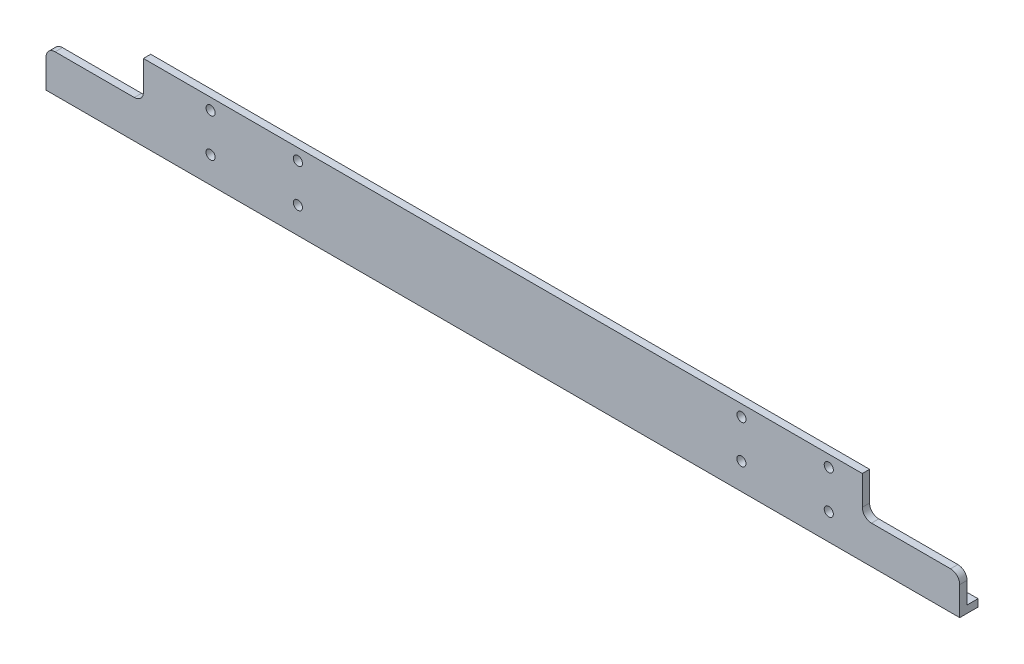
SolidWorks part; units mm, degrees
ref_plane "Front" through (0, 0, 0) normal (0, 0, 1) x (1, 0, 0)
ref_plane "Top" through (0, 0, 0) normal (0, 1, 0) x (1, 0, 0)
ref_plane "Right" through (0, 0, 0) normal (1, 0, 0) x (0, 0, -1)
ref_axis "side-side" through (80.9, 0, 0) along (-1, 0, 0)
ref_axis "up-down" through (0, 50, 0) along (0, -1, 0)
ref_axis "front-back" through (0, 0, -80.9) along (0, 0, 1)
sketch "Sketch1" plane through (0, 0, 0) normal (1, 0, 0) x (0, 0, -1)
  line L1 (0, 0) -> (31.75, 0)
  line L2 (0, 0) -> (0, 31.75)
  line L3 (0, 31.75) -> (3.048, 31.75)
  line L4 (31.75, 0) -> (31.75, 3.048)
  line L5 (3.048, 3.048) -> (31.75, 3.048)
  line L6 (3.048, 3.048) -> (3.048, 31.75)
  dimension "D1" = 31.75
  dimension "D2" = 3.048
extrude "Boss-Extrude1" add sketch "Sketch1" along normal mid plane 381
sketch "Sketch2" plane through (0, 0, 0) normal (0, 0, 1) x (1, 0, 0)
  line L2 (152.877, 19.5) -> (185.5, 19.5)
  line L3 (149.877, 32) -> (149.877, 22.5)
  line L6 (174.5, 4) -> (174.5, 0)
  line L7 (172.5, 4) -> (174.5, 4)
hole_wizard "#6 Clearance Hole1" positions "Sketch4" profile "Sketch3" hole size "#6" standard "ANSI Inch" end condition through all
sketch "Sketch4" plane through (0, 0, 0) normal (0, 0, 1) x (1, 0, 0)
  point P0 (135.9, 27)
  point P3 (135.9, 11)
  point P6 (99.5, 27)
  point P9 (99.468, 11)
  point P12 (-121.868, 27)
  point P15 (-121.868, 11)
  point P18 (-85.468, 11)
  point P21 (-85.468, 27)
sketch "Sketch3" plane through (135.9, 27, 0) normal (1, 0, 0) x (0, -1, 0)
  line L0 (0, 0) -> (0, 31.75)
  line L1 (0, 31.75) -> (1.8986, 31.75)
  line L2 (1.8986, 31.75) -> (1.8986, 0)
  line L5 (1.8986, 0) -> (0, 0)
  line L11 (0, -6.35) -> (0, 107.95) construction
  dimension "Thru Hole Dia." = 3.7973
  dimension "Thru Hole Depth" = 31.75
sketch "Sketch5" plane through (0, 0, 0) normal (0, 0, 1) x (1, 0, 0)
  line L0 (149.877, 32) -> (149.877, 22.5) construction
  line L2 (149.877, 41.148) -> (149.877, 19.558)
  line L3 (153.687, 15.748) -> (186.69, 15.748)
  line L4 (0, 0) -> (0, 88.4721) construction
  line L5 (190.5, 31.75) -> (190.5, 0) construction
  line L6 (190.5, 11.938) -> (190.5, -9.652)
  line L7 (190.5, 0) -> (-190.5, 0) construction
  line L8 (-198.12, 41.148) -> (-149.877, 41.148)
  line L9 (198.12, -9.652) -> (190.5, -9.652)
  line L10 (198.12, -9.652) -> (198.12, 41.148)
  line L11 (198.12, 41.148) -> (149.877, 41.148)
  line L12 (-198.12, -9.652) -> (-198.12, 41.148)
  line L13 (-198.12, -9.652) -> (-190.5, -9.652)
  line L14 (-190.5, 11.938) -> (-190.5, -9.652)
  line L15 (-153.687, 15.748) -> (-186.69, 15.748)
  line L16 (-149.877, 41.148) -> (-149.877, 19.558)
  arc A0 (149.877, 19.558) -> (153.687, 15.748) centre (153.687, 19.558) ccw
  arc A1 (190.5, 11.938) -> (186.69, 15.748) centre (186.69, 11.938) ccw
  arc A2 (-190.5, 11.938) -> (-186.69, 15.748) centre (-186.69, 11.938) cw
  arc A3 (-149.877, 19.558) -> (-153.687, 15.748) centre (-153.687, 19.558) cw
  dimension "D1" = 3.81
  dimension "D3" = 3.81
  dimension "D2" = 15.748
  dimension "D4" = 25.4
  dimension "D5" = 7.62
  dimension "D6" = 25.4
extrude "Cut-Extrude1" cut sketch "Sketch5" against normal through all
sketch "Sketch6" plane through (0, 0, 0) normal (1, 0, 0) x (0, 0, -1)
  line L0 (0, 50) -> (0, -50) construction
  line L1 (7.62, 7.62) -> (33.02, 7.62)
  line L2 (7.62, 7.62) -> (7.62, -7.62)
  line L3 (7.62, -7.62) -> (33.02, -7.62)
  line L4 (33.02, 7.62) -> (33.02, -7.62)
  line L5 (50, 0) -> (-50, 0) construction
  dimension "D1" = 7.62
  dimension "D2" = 25.4
  dimension "D3" = 7.62
  dimension "D4" = 7.62
extrude "Cut-Extrude2" cut sketch "Sketch6" against normal through all and the other way through all
